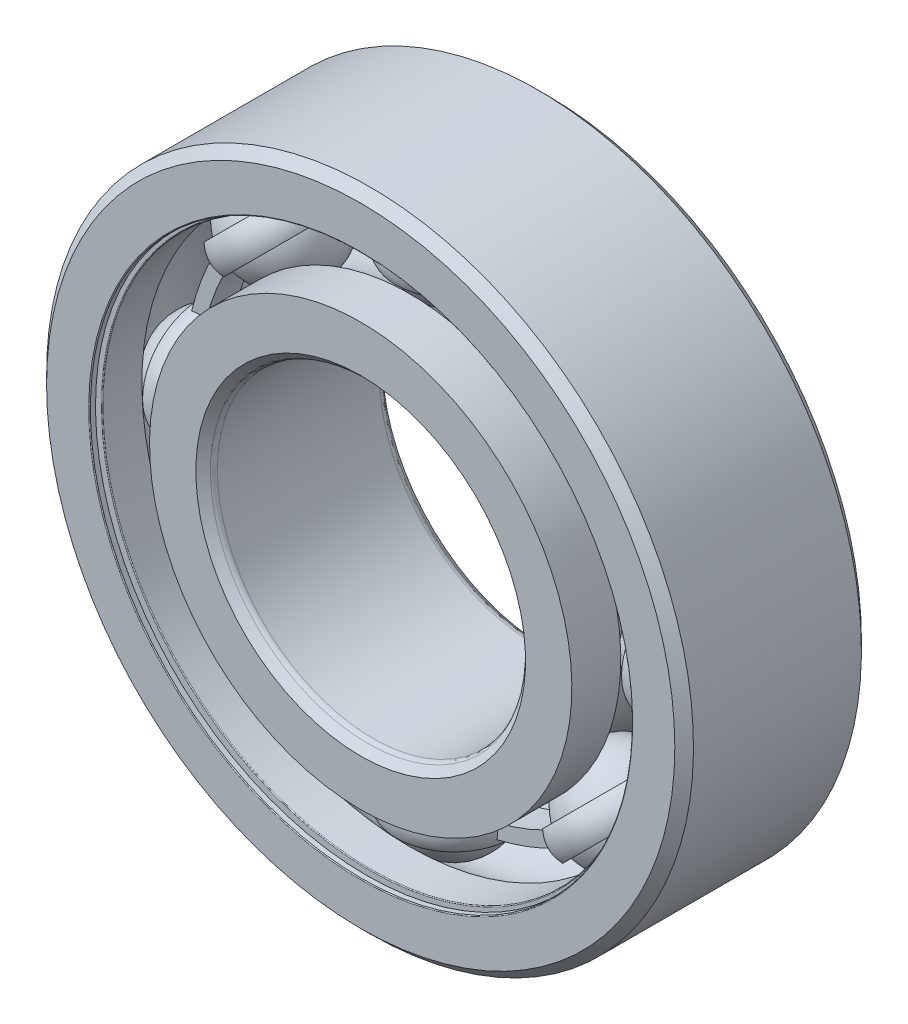
SolidWorks part; units mm, degrees
ref_plane "Front Plane" through (0, 0, 0) normal (0, 0, 1) x (1, 0, 0)
ref_plane "Top Plane" through (0, 0, 0) normal (0, 1, 0) x (1, 0, 0)
ref_plane "Right Plane" through (0, 0, 0) normal (1, 0, 0) x (0, 0, -1)
sketch "Sketch1" plane through (0, 0, 0) normal (0, 0, 1) x (1, 0, 0)
  line L0 (-26, 0) -> (26, 0) construction
  line L1 (-12.5, 0) -> (12.5, 0) construction
  circle A0 centre (0, 0) radius 12.5 construction
  circle A1 centre (0, 0) radius 26 construction
  point P3 (0, 0)
  point P6 (0, 0)
  point P7 (0, -12.5)
  point P11 (0, -26)
  point P12 (0, 12.5)
  point P13 (0, 26)
  dimension "OD" = 52
  dimension "ID" = 25
sketch "Sketch2" plane through (0, 0, 0) normal (1, 0, 0) x (0, 0, -1)
  line L0 (-7.5, 26) -> (7.5, 26) construction
  line L1 (0, 26) -> (0, -26) construction
  line L2 (6.75, 26) -> (-6.75, 26)
  line L3 (-6.75, 26) -> (-7.5, 25.25)
  line L4 (-7.5, 25.25) -> (-7.5, 21.5269)
  line L5 (-7.5, 21.5269) -> (-3.5625, 21.5269)
  line L6 (7.5, 21.5269) -> (3.5625, 21.5269)
  line L7 (7.5, 25.25) -> (7.5, 21.5269)
  line L8 (6.75, 26) -> (7.5, 25.25)
  line L9 (0, 26) -> (0, 19.25) construction
  line L10 (0, 19.25) -> (0, 12.5) construction
  line L11 (0, 26) -> (0, -26) construction
  line L12 (-7.5, 0) -> (7.5, 0) construction
  line L13 (7.5, 12.5) -> (-7.5, 12.5) construction
  line L14 (0, 23.478) -> (0, 15.022) construction
  line L15 (-7.5, -12.5) -> (7.5, -12.5) construction
  line L16 (-7.5, -12.5) -> (-7.5, 12.5) construction
  line L17 (7.5, 26) -> (7.5, -26) construction
  arc A0 (-3.5625, 21.5269) -> (3.5625, 21.5269) centre (0, 19.25) cw
  circle A1 centre (0, 19.25) radius 4.228 construction
  point P14 (0, 12.5)
  point P17 (0, 0)
  point P21 (0, 26)
  point P29 (0, 12.5)
  point P30 (0, -12.5)
  point P35 (0, 23.478)
  dimension "Approx. Ball Dia." = 8.456
  dimension "Width" = 15
  dimension "D1" = 45
  dimension "D2" = 0.75
  dimension "D3" = 7.125
  dimension "D4" = 2.2769
  dimension "For Shaft Diameter" = 25
  dimension "For Housing ID" = 52
sketch "Sketch3" plane through (0, 0, 0) normal (1, 0, 0) x (0, 0, -1)
  line L0 (6.75, 26) -> (7.5, 25.25) construction
  line L1 (7.5, 25.25) -> (7.5, 21.5269) construction
  line L2 (7.5, 21.5269) -> (3.5625, 21.5269) construction
  line L3 (-7.5, 21.5269) -> (-3.5625, 21.5269) construction
  line L4 (-7.5, 25.25) -> (-7.5, 21.5269) construction
  line L5 (-6.75, 26) -> (-7.5, 25.25) construction
  line L6 (6.75, 26) -> (-6.75, 26) construction
  line L7 (6.75, 26) -> (7.5, 25.25)
  line L8 (7.5, 25.25) -> (7.5, 21.5269)
  line L9 (7.5, 21.5269) -> (3.5625, 21.5269)
  line L10 (-7.5, 21.5269) -> (-3.5625, 21.5269)
  line L11 (-7.5, 25.25) -> (-7.5, 21.5269)
  line L12 (-6.75, 26) -> (-7.5, 25.25)
  line L13 (6.75, 26) -> (-6.75, 26)
  arc A0 (3.5625, 21.5269) -> (-3.5625, 21.5269) centre (0, 19.25) ccw construction
  arc A1 (3.5625, 21.5269) -> (-3.5625, 21.5269) centre (0, 19.25) ccw
revolve "Revolve1" add sketch "Sketch3" angle 360 about L12
sketch "Sketch8" plane through (0, 0, 0) normal (1, 0, 0) x (0, 0, -1)
  line L0 (-7.5, 21.5269) -> (-3.5625, 21.5269) construction
  line L1 (-7.02, 21.5269) -> (-6.75, 21.5269)
  line L2 (-7.02, 21.5269) -> (-7.02, 23.0179) construction
  line L3 (-7.02, 23.0179) -> (-6.75, 23.0179)
  line L4 (-6.75, 21.5269) -> (-6.75, 23.0179)
  line L5 (7.5, 21.5269) -> (3.5625, 21.5269) construction
  line L6 (6.75, 21.5269) -> (7.02, 21.5269)
  line L7 (6.75, 21.5269) -> (6.75, 23.0179)
  line L8 (6.75, 23.0179) -> (7.02, 23.0179)
  line L9 (7.02, 21.5269) -> (7.02, 23.0179) construction
  line L10 (-6.75, 23.0179) -> (6.75, 23.0179) construction
  line L11 (0, 26) -> (0, -26) construction
  line L12 (-7.02, 23.0179) -> (-7.02, 24.509) construction
  line L13 (-7.02, 24.509) -> (-7.02, 26) construction
  line L14 (-7.5, 26) -> (7.5, 26) construction
  line L15 (-7.02, 21.5269) -> (-7.5, 21.5269)
  line L16 (-7.5, 21.5269) -> (-7.5, 21.7969)
  line L17 (-7.5, 25.25) -> (-7.5, 21.5269) construction
  line L18 (-7.5, 21.7969) -> (-7.02, 21.7969)
  line L19 (-7.02, 21.7969) -> (-7.02, 23.0179)
  line L20 (7.02, 21.5269) -> (7.5, 21.5269)
  line L21 (7.5, 21.5269) -> (7.5, 21.7969)
  line L22 (7.5, 25.25) -> (7.5, 21.5269) construction
  line L23 (7.5, 21.7969) -> (7.02, 21.7969)
  line L24 (7.02, 21.7969) -> (7.02, 23.0179)
  point P12 (0, 23.0179)
  dimension "D1" = 13.5
  dimension "D2" = 0.27
revolve "Cut-Revolve1" cut sketch "Sketch8" angle 360 about L12
sketch "Sketch4" plane through (0, 0, 0) normal (1, 0, 0) x (0, 0, -1)
  line L0 (0, 26) -> (0, -26) construction
  line L1 (0, 26) -> (0, -26) construction
  line L2 (-6.75, 12.5) -> (-7.5, 13.25)
  line L3 (-7.5, 13.25) -> (-7.5, 16.9731)
  line L5 (-7.5, 16.9731) -> (-3.5625, 16.9731)
  line L6 (-6.75, 12.5) -> (6.75, 12.5)
  line L8 (6.75, 12.5) -> (7.5, 13.25)
  line L10 (7.5, 13.25) -> (7.5, 16.9731)
  line L11 (7.5, 16.9731) -> (3.5625, 16.9731)
  line L12 (-7.5, 25.25) -> (-7.5, 21.5269) construction
  line L13 (6.75, 26) -> (7.5, 25.25) construction
  line L15 (7.5, -25.25) -> (7.5, 25.25) construction
  line L16 (6.75, 26) -> (6.75, -26) construction
  arc A1 (3.5625, 16.9731) -> (-3.5625, 16.9731) centre (0, 19.25) cw
  circle A2 centre (0, 19.25) radius 4.228 construction
  point P1 (0, 12.5)
revolve "Revolve2" add sketch "Sketch4" angle 360 about L12
sketch "Sketch5" plane through (0, 0, 0) normal (1, 0, 0) x (0, 0, -1)
  line L0 (-4.228, 19.25) -> (4.228, 19.25)
  arc A2 (-4.228, 19.25) -> (4.228, 19.25) centre (0, 19.25) cw
  arc A3 (3.5625, 21.5269) -> (-3.5625, 21.5269) centre (0, 19.25) ccw construction
revolve "Revolve3" add sketch "Sketch5" angle 360 about L0
sketch "Sketch6" plane through (0, 0, 0) normal (1, 0, 0) x (0, 0, -1)
  line L0 (-3.5625, 21.5269) -> (-3.5625, 20.3885) construction
  line L1 (-3.5625, 20.3885) -> (-3.5625, 19.25) construction
  line L2 (-3.5625, 19.25) -> (-3.5625, 18.1115) construction
  line L3 (-3.5625, 18.1115) -> (-3.5625, 16.9731) construction
  line L4 (-7.5, 20.3885) -> (-6.9286, 20.3885) construction
  line L5 (-3.5625, 20.3885) -> (-3.5625, 18.1115) construction
  line L7 (-6.9286, 20.3885) -> (-6.3573, 20.3885) construction
  line L8 (-6.3573, 20.3885) -> (-5.7859, 20.3885) construction
  line L10 (0, 26) -> (0, -26) construction
  line L11 (0, 26) -> (0, -26) construction
  line L12 (-7.5, 21.5269) -> (-7.5, 20.3885) construction
  line L13 (-4.6432, 20.3885) -> (-4.0718, 20.3885) construction
  line L14 (-7.5, 25.25) -> (-7.5, -25.25) construction
  line L15 (-7.5, 20.3885) -> (-7.5, 19.25) construction
  line L16 (-7.5, 19.25) -> (-7.5, 18.1115) construction
  line L17 (-7.5, 18.1115) -> (-7.5, 16.9731) construction
  line L18 (-5.7859, 20.3885) -> (-5.2145, 20.3885) construction
  line L19 (-5.2145, 20.3885) -> (-4.6432, 20.3885) construction
  line L20 (-4.0718, 20.3885) -> (-4.6432, 20.3885)
  line L21 (-7.5, 18.1115) -> (-6.9286, 18.1115) construction
  line L22 (-6.9286, 18.1115) -> (-6.3573, 18.1115) construction
  line L23 (-6.3573, 18.1115) -> (-5.7859, 18.1115) construction
  line L24 (-5.7859, 18.1115) -> (-5.2145, 18.1115) construction
  line L25 (-5.2145, 18.1115) -> (-4.6432, 18.1115) construction
  line L26 (-4.6432, 18.1115) -> (-4.0718, 18.1115) construction
  line L27 (-4.0718, 18.1115) -> (-4.6432, 18.1115)
  line L28 (-5.2145, 20.3885) -> (-5.2145, 18.1115) construction
  line L30 (-4.9289, 20.3885) -> (-4.9289, 18.1115) construction
  circle A0 centre (0, 19.25) radius 4.228 construction
  arc A2 (-4.6432, 18.1115) -> (-4.6432, 20.3885) centre (-2.5176, 19.25) cw
  arc A3 (-4.0718, 20.3885) -> (-4.0718, 18.1115) centre (0, 19.25) ccw
revolve "Revolve4" add sketch "Sketch6" angle 360 about L11
sketch "Sketch7" plane through (0, 0, 0) normal (0, 0, 1) x (1, 0, 0)
  line L0 (-4.228, 19.25) -> (4.228, 19.25) construction
  line L1 (0, 15.022) -> (0, 23.478) construction
  line L2 (0, 0) -> (7.612, 17.681) construction
  line L8 (0, 26) -> (0, -26) construction
  line L9 (13.9832, 13.2299) -> (14.8102, 14.0124)
  line L10 (0, 26) -> (0, -26) construction
  line L11 (0, 20.3885) -> (0, 19.25)
  arc A1 (13.9832, 13.2299) -> (0, 19.25) centre (0, 0) ccw
  arc A2 (14.8102, 14.0124) -> (0, 20.3885) centre (0, 0) ccw
  dimension "D1" = 46.586
  dimension "D2" = 8.456
extrude "Boss-Extrude1" add sketch "Sketch7" along normal mid plane 2.5
pattern_circular "CirPattern1" count 8 over 360 about axis through (0, 0, 7.5) along (0, 0, -1) of bodies 104 134
pattern_circular "CirPattern2" count 8 over 360 about axis through (0, 0, 7.5) along (0, 0, -1) of "Revolve4", "Boss-Extrude1" reverse direction yes
fillet "Fillet1" radius 0.0675 4 edges at (0, -21.5269, -6.75) (0, -21.7969, -7.5) (0, -21.5269, 6.75) (0, -21.7969, 7.5)
fillet "Fillet2" radius 0.5625 2 edges at (0, -12.5, -6.75) (0, -12.5, 6.75)
ref_plane "Plane1" through (7.612, 17.681, 0) normal (0.3954, 0.9185, 0) x (0.9185, -0.3954, 0)
sketch "Sketch9" plane through (7.612, 17.681, 0) normal (0.3954, 0.9185, 0) x (0.9185, -0.3954, 0)
  line L0 (-3.7287, -1.25) -> (-3.7287, -3.75)
  line L1 (-3.7287, -3.75) -> (-1.6174, -3.75)
  line L2 (-1.6174, -3.75) -> (0, -2.3929)
  line L3 (0, -2.3929) -> (1.6174, -3.75)
  line L4 (1.6174, -3.75) -> (3.7287, -3.75)
  line L5 (3.7287, -3.75) -> (3.7287, -1.25)
  line L6 (3.7287, -1.25) -> (-3.7287, -1.25)
  line L7 (0, -1.25) -> (0, 0) construction
  line L8 (-3.7287, -1.25) -> (-3.7287, 0) construction
  dimension "D1" = 2.5
  dimension "D2" = 1.25
  dimension "D3" = 40
extrude "Boss-Extrude2" [suppressed] add sketch "Sketch9" along normal blind 3.6995 draft 15 and the other way blind 3.6995 draft 10 separate body draft outward yes other way draft outward yes
fillet "Fillet3" [suppressed] radius 0.75
mirror "Mirror1" [suppressed] about plane through (0, 0, 0) normal (0, 0, 1) of bodies 149
pattern_circular "CirPattern3" [suppressed] count 8 over 360 about axis through (0, 0, 7.5) along (0, 0, -1) of bodies 158 149
equation "\"D2@Sketch2\" = \"Width@Sketch2\" * .05"
equation "\"D3@Sketch2\"=\"Width@Sketch2\" * .475"
equation "\"D4@Sketch2\" =  (  (  ( \"OD@Sketch1\" - \"Width@Sketch2\" )  / 2 )  / 3.25 )  / 2.5"
equation "\"D1@Boss-Extrude1\" = \"Width@Sketch2\" / 6"
equation "\"D1@Sketch8\"=\"Width@Sketch2\"*.9"
equation "\"D2@Sketch8\"=\"D1@Sketch8\"*.02"
equation "\"D1@Fillet1\" = \"D2@Sketch8\" * .25"
equation "\"D1@Fillet2\" = \"D2@Sketch2\" * .75"
equation "\"Approx No of Balls\"= ( pi * \"OD@Sketch1\" ) * .4 / \"Approx. Ball Dia.@Sketch2\""
equation "\"D1@CirPattern1\"=\"Approx No of Balls\""
equation "\"D1@Sketch7\"=360/\"Approx No of Balls\""
equation "\"D1@CirPattern2\"=\"Approx No of Balls\""
equation "\"D2@Sketch7\"=\"Approx. Ball Dia.@Sketch2\""
equation "\"D2@Sketch9\"=\"d1@boss-extrude1\"*.5"
equation "\"D1@Sketch9\"=\"D2@Sketch9\"*2"
equation "\"D1@Boss-Extrude2\"=\"Approx. Ball Dia.@Sketch2\"*.4375"
equation "\"D2@Boss-Extrude2\"=\"D1@Boss-Extrude2\""
equation "\"D1@CirPattern3\"=\"Approx No of Balls\""
equation "\"D1@Fillet3\"=\"D1@Sketch9\" * .3"
